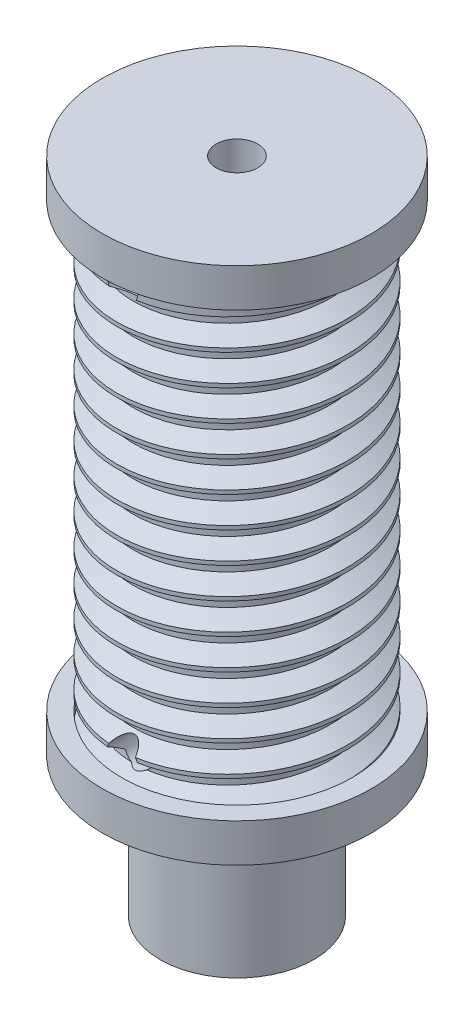
SolidWorks part; units mm, degrees
material "ABS"
ref_plane "Front Plane" through (0, 0, 0) normal (0, 0, 1) x (1, 0, 0)
ref_plane "Top Plane" through (0, 0, 0) normal (0, 1, 0) x (1, 0, 0)
ref_plane "Right Plane" through (0, 0, 0) normal (1, 0, 0) x (0, 0, -1)
sketch "Sketch1" plane through (0, 0, 0) normal (0, 1, 0) x (1, 0, 0)
  line L1 (3.5855, -6.0628) -> (7.0433, 0.0738)
  line L2 (7.0433, 0.0738) -> (3.4578, 6.1365)
  line L3 (3.4578, 6.1365) -> (-3.5855, 6.0628)
  line L4 (-3.5855, 6.0628) -> (-7.0433, -0.0738)
  line L5 (-7.0433, -0.0738) -> (-3.4578, -6.1365)
  line L6 (-3.4578, -6.1365) -> (3.5855, -6.0628)
  circle A0 centre (0, 0) radius 6.1 construction
  circle A1 centre (0, 0) radius 10
  dimension "D2" = 20
  dimension "D1" = 12.2
extrude "Boss-Extrude1" add sketch "Sketch1" along normal blind 18 contours A1 L6 L5 L4 L3 L2 L1 region at (-9.7172, 0, 0)
sketch "Sketch2" plane through (0, 18, 0) normal (0, 1, 0) x (1, 0, 0)
  circle A0 centre (0, 0) radius 17.5
  dimension "D1" = 35
extrude "Boss-Extrude2" add sketch "Sketch2" along normal blind 5
sketch "Sketch3" plane through (-5.3144, 0, -2.9945) normal (0.8712, 0, 0.4909) x (0.4909, 0, -0.8712)
  line L0 (-3.5218, 18) -> (3.5218, 18) construction
  line L1 (0, 18) -> (0, -0.0617) construction
  circle A0 centre (0, 5) radius 1.75
  dimension "D1" = 3.5
  dimension "D2" = 13
extrude "Cut-Extrude1" cut sketch "Sketch3" against normal blind 120
sketch "Sketch4" plane through (0, 23, 0) normal (0, 1, 0) x (1, 0, 0)
  circle A0 centre (0, 0) radius 15
  dimension "D1" = 30
extrude "Boss-Extrude3" add sketch "Sketch4" along normal blind 120
sketch "Sketch6" plane through (0, 143, 0) normal (0, 1, 0) x (1, 0, 0)
  circle A0 centre (0, 0) radius 10
  dimension "D1" = 20
extrude "Cut-Extrude3" cut sketch "Sketch6" against normal up to surface (120 mm away) contours A0 up to face at (0, 23, 15)
sketch "Sketch5" plane through (0, 143, 0) normal (0, 1, 0) x (1, 0, 0)
  circle A0 centre (0, 0) radius 15
  dimension "D1" = 30
extrude "Boss-Extrude4" add sketch "Sketch5" along normal blind 5
sketch "Sketch7" plane through (0, 148, 0) normal (0, 1, 0) x (1, 0, 0)
  circle A0 centre (0, 0) radius 2.7
  dimension "D1" = 5.4
extrude "Cut-Extrude4" cut sketch "Sketch7" against normal through all
ref_plane "Plane1" through (0, 83, 0) normal (0, 1, 0) x (1, 0, 0)
sketch "Sketch9" plane through (0, 83, 0) normal (0, 1, 0) x (1, 0, 0)
  circle A0 centre (0, 0) radius 17.5
  dimension "D1" = 35
extrude "Boss-Extrude5" add sketch "Sketch9" along normal blind 2.5 and the other way blind 2.5 contours A0
sketch "Sketch10" plane through (0, 0, 0) normal (0, 0, 1) x (1, 0, 0)
  line L0 (0, 148) -> (0, 23) construction
  line L1 (2.7, 148) -> (-2.7, 148) construction
  line L2 (17.5, 23) -> (-17.5, 23) construction
  line L3 (-15, 80.5) -> (15, 80.5) construction
  circle A0 centre (0, 25) radius 2
  circle A1 centre (0, 87.5) radius 2
  circle A2 centre (0, 78.5) radius 2
  dimension "D1" = 4
  dimension "D2" = 4
extrude "Cut-Extrude5" cut sketch "Sketch10" against normal through all and the other way through all
sketch "Sketch11" plane through (0, 0, 0) normal (0, 0, 1) x (1, 0, 0)
  line L0 (0, 0) -> (0, 148) construction
  line L1 (15, 148) -> (-15, 148) construction
sketch "Sketch12" plane through (0, 85.5, 0) normal (0, 1, 0) x (1, 0, 0)
  circle A0 centre (0, 0) radius 20.9831
extrude "Cut-Extrude6" cut sketch "Sketch12" along normal blind 80
sketch "Sketch13" plane through (0, 85.5, 0) normal (0, 1, 0) x (1, 0, 0)
  circle A0 centre (0, 0) radius 2.7 construction
  circle A1 centre (0, 0) radius 2.7
extrude "Cut-Extrude7" cut sketch "Sketch13" against normal blind 20
sketch "Sketch20" plane through (0, 80.5, 0) normal (0, -1, 0) x (1, 0, 0)
  circle A0 centre (0, 0) radius 2.7
  circle A1 centre (0, 0) radius 10
  circle A2 centre (0, 0) radius 10 construction
extrude "Boss-Extrude6" add sketch "Sketch20" along normal blind 10
sketch "Sketch21" plane through (0, 0, 0) normal (0, 0, 1) x (1, 0, 0)
  circle A0 centre (0, 78.5) radius 2 construction
  circle A1 centre (0, 78.5) radius 2
extrude "Cut-Extrude8" cut sketch "Sketch21" against normal blind 60 and the other way blind 30
thread "Thread1" pitch 4 method cut profile "Thread Profile1" start angle 0, offset 0, length 0, pitch 4, diameter 30
ref_plane "Plane2" through (-15, 80.5, 0) normal (0, 0, 1) x (-1, 0, 0)
sketch "Thread Profile1" plane through (-15, 80.5, 0) normal (0, 0, 1) x (-1, 0, 0)
  line L0 (0, 0) -> (0, 4) construction
  line L11 (0, 0) -> (0, 3.5)
  line L12 (0, 3.5) -> (-2.1651, 2.25)
  line L13 (-2.1651, 2.25) -> (-2.1651, 1.25)
  line L15 (-2.1651, 1.25) -> (0, 0)
  line L17 (-2.1651, 1.75) -> (0, 1.75) construction
  point P2 (0, 0)
  dimension "Pitch" = 4
  dimension "Profile_Angle" = 60
  dimension "Profile_Land" = 1
  dimension "Profile_Height" = 2.1651
